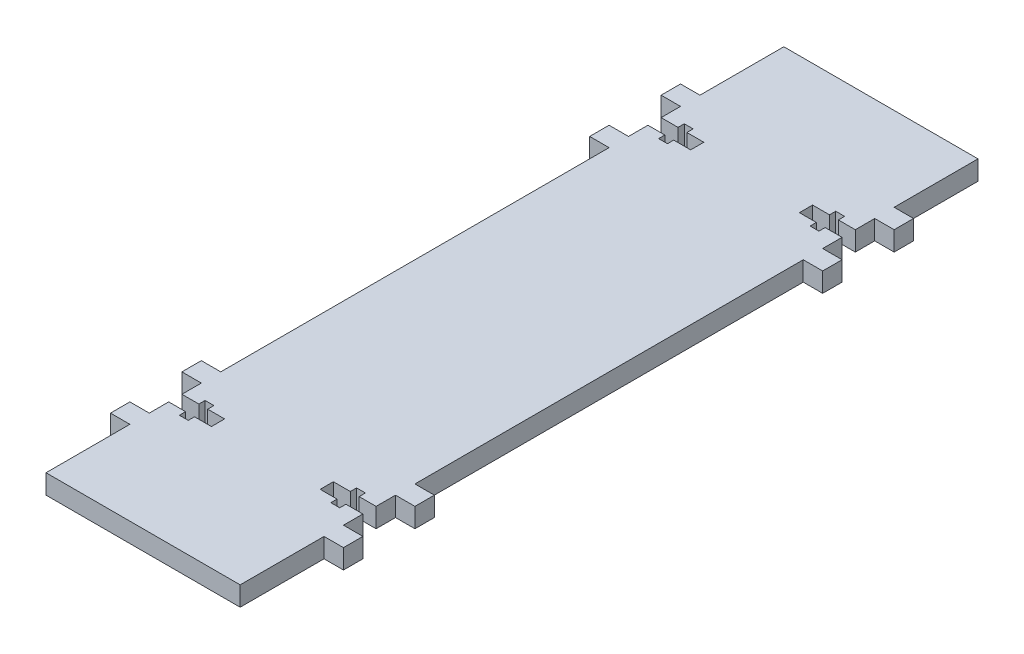
SolidWorks part; units mm, degrees
ref_plane "Front Plane" through (0, 0, 0) normal (0, 0, 1) x (1, 0, 0)
ref_plane "Top Plane" through (0, 0, 0) normal (0, 1, 0) x (1, 0, 0)
ref_plane "Right Plane" through (0, 0, 0) normal (1, 0, 0) x (0, 0, -1)
sketch "Elevator Belt Backplate" plane through (0, 0, 0) normal (0, 1, 0) x (1, 0, 0)
  line L0 (-31.75, -63.5) -> (-31.75, 63.5)
  line L1 (-31.75, -120.65) -> (31.75, -120.65)
  line L2 (-31.75, -93.218) -> (-31.75, -120.65)
  line L3 (-31.75, 120.65) -> (31.75, 120.65)
  line L4 (31.75, -120.65) -> (31.75, -93.218)
  line L5 (-31.75, -120.65) -> (31.75, 120.65) construction
  line L6 (-31.75, 120.65) -> (31.75, -120.65) construction
  line L7 (31.75, 93.218) -> (31.75, 120.65)
  line L9 (0, 120.65) -> (0, -120.65) construction
  line L21 (-31.75, 93.218) -> (-31.75, 120.65)
  line L70 (31.75, -63.5) -> (31.75, 63.5)
  point P0 (0, 0)
  line B0 (31.75, 69.85) -> (38.1, 69.85)
  line B1 (38.1, 69.85) -> (38.1, 63.5)
  line B2 (38.1, 63.5) -> (31.75, 63.5)
  line B3 (31.75, 76.2) -> (26.215, 76.2)
  line B4 (26.215, 76.2) -> (26.215, 74.159)
  line B5 (26.215, 74.159) -> (23.315, 74.159)
  line B6 (23.315, 74.159) -> (23.315, 76.2)
  line B7 (23.315, 76.2) -> (17.78, 76.2)
  line B8 (17.78, 76.2) -> (17.78, 80.518)
  line B9 (17.78, 80.518) -> (23.315, 80.518)
  line B10 (23.315, 80.518) -> (23.315, 82.559)
  line B11 (23.315, 82.559) -> (26.215, 82.559)
  line B12 (26.215, 82.559) -> (26.215, 80.518)
  line B13 (26.215, 80.518) -> (31.75, 80.518)
  line B14 (17.78, 78.359) -> (31.75, 78.359) construction
  line B15 (31.75, 86.868) -> (31.75, 80.518)
  line B16 (38.1, 93.218) -> (31.75, 93.218)
  line B17 (31.75, 69.85) -> (31.75, 76.2)
  line B18 (38.1, 86.868) -> (38.1, 93.218)
  line B19 (31.75, 86.868) -> (38.1, 86.868)
  line B20 (31.75, -69.85) -> (38.1, -69.85)
  line B21 (38.1, -69.85) -> (38.1, -63.5)
  line B22 (38.1, -63.5) -> (31.75, -63.5)
  line B23 (31.75, -76.2) -> (26.215, -76.2)
  line B24 (26.215, -76.2) -> (26.215, -74.159)
  line B25 (26.215, -74.159) -> (23.315, -74.159)
  line B26 (23.315, -74.159) -> (23.315, -76.2)
  line B27 (23.315, -76.2) -> (17.78, -76.2)
  line B28 (17.78, -76.2) -> (17.78, -80.518)
  line B29 (17.78, -80.518) -> (23.315, -80.518)
  line B30 (23.315, -80.518) -> (23.315, -82.559)
  line B31 (23.315, -82.559) -> (26.215, -82.559)
  line B32 (26.215, -82.559) -> (26.215, -80.518)
  line B33 (26.215, -80.518) -> (31.75, -80.518)
  line B34 (17.78, -78.359) -> (31.75, -78.359) construction
  line B35 (31.75, -86.868) -> (31.75, -80.518)
  line B36 (38.1, -93.218) -> (31.75, -93.218)
  line B37 (31.75, -69.85) -> (31.75, -76.2)
  line B38 (38.1, -86.868) -> (38.1, -93.218)
  line B39 (31.75, -86.868) -> (38.1, -86.868)
  line B40 (-31.75, -69.85) -> (-38.1, -69.85)
  line B41 (-38.1, -69.85) -> (-38.1, -63.5)
  line B42 (-38.1, -63.5) -> (-31.75, -63.5)
  line B43 (-31.75, -76.2) -> (-26.215, -76.2)
  line B44 (-26.215, -76.2) -> (-26.215, -74.159)
  line B45 (-26.215, -74.159) -> (-23.315, -74.159)
  line B46 (-23.315, -74.159) -> (-23.315, -76.2)
  line B47 (-23.315, -76.2) -> (-17.78, -76.2)
  line B48 (-17.78, -76.2) -> (-17.78, -80.518)
  line B49 (-17.78, -80.518) -> (-23.315, -80.518)
  line B50 (-23.315, -80.518) -> (-23.315, -82.559)
  line B51 (-23.315, -82.559) -> (-26.215, -82.559)
  line B52 (-26.215, -82.559) -> (-26.215, -80.518)
  line B53 (-26.215, -80.518) -> (-31.75, -80.518)
  line B54 (-17.78, -78.359) -> (-31.75, -78.359) construction
  line B55 (-31.75, -86.868) -> (-31.75, -80.518)
  line B56 (-38.1, -93.218) -> (-31.75, -93.218)
  line B57 (-31.75, -69.85) -> (-31.75, -76.2)
  line B58 (-38.1, -86.868) -> (-38.1, -93.218)
  line B59 (-31.75, -86.868) -> (-38.1, -86.868)
  line B60 (-31.75, 69.85) -> (-38.1, 69.85)
  line B61 (-38.1, 69.85) -> (-38.1, 63.5)
  line B62 (-38.1, 63.5) -> (-31.75, 63.5)
  line B63 (-31.75, 76.2) -> (-26.215, 76.2)
  line B64 (-26.215, 76.2) -> (-26.215, 74.159)
  line B65 (-26.215, 74.159) -> (-23.315, 74.159)
  line B66 (-23.315, 74.159) -> (-23.315, 76.2)
  line B67 (-23.315, 76.2) -> (-17.78, 76.2)
  line B68 (-17.78, 76.2) -> (-17.78, 80.518)
  line B69 (-17.78, 80.518) -> (-23.315, 80.518)
  line B70 (-23.315, 80.518) -> (-23.315, 82.559)
  line B71 (-23.315, 82.559) -> (-26.215, 82.559)
  line B72 (-26.215, 82.559) -> (-26.215, 80.518)
  line B73 (-26.215, 80.518) -> (-31.75, 80.518)
  line B74 (-17.78, 78.359) -> (-31.75, 78.359) construction
  line B75 (-31.75, 86.868) -> (-31.75, 80.518)
  line B76 (-38.1, 93.218) -> (-31.75, 93.218)
  line B77 (-31.75, 69.85) -> (-31.75, 76.2)
  line B78 (-38.1, 86.868) -> (-38.1, 93.218)
  line B79 (-31.75, 86.868) -> (-38.1, 86.868)
  dimension "D1" = 63.5
  dimension "D2" = 63.5
  dimension "D4" = 63.5
  dimension "D5" = 241.3
sketch_block_instance "Male T-slot assembly-1"
sketch_block "Male T-slot assembly" parameters "D1"=6.35, "D2"=6.35, "D3"=4.318, "D4"=2.9, "D5"=8.4, "D6"=13.97, "D7"=6.35
sketch_block_instance "Male T-slot assembly-3"
sketch_block_instance "Male T-slot assembly-10"
sketch_block_instance "Male T-slot assembly-11"
extrude "Boss-Extrude1" add sketch "Elevator Belt Backplate" along normal blind 6.35 contours B79 B75 B73 B72 B71 B70 B69 B68 B67 B66 B65 B64 B63 B77 B60 B61 B62 L0 B42 B41 B40 B57 B43 B44 B45 B46 B47 B48 B49 B50 B51 B52 B53 B55 B59 B58 B56 L2 L1 L4 B36 B38 B39 B35 B33 B32 B31 B30 B29 B28 B27 region at (0, 0, 0)
equation "\"Ball Diameter\"= 1.75in"
equation "\"Sheet Thickness\"= 0.25in"
equation "\"Screw Diameter\"= .17in"
equation "\"Robot Diameter\"= 14in"
equation "\"Castor Screw Diameter\"= 0.22in"
equation "\"Wheel Diameter\" = 4in"
equation "\"Nut Diameter\" = 8.4mm"
equation "\"Nut Height\" = 2.9mm"
equation "\"Screw Height\" = 0.55in"
equation "\"Pulley Diameter\" = 1in"
equation "\"Reactor Height\" = 14in"
equation "\"Elevator Height\" = 11.5in"
equation "\"Elevator Width\" = \"Ball Diameter\" + 0.25in"
equation "\"Elevator Bearing Diameter\" = sqr(2*(\"Sheet Thickness\"^2)) + 0.2in"
equation "\"Elevator Axle Length\" = \"Elevator Width\" + 8*\"Sheet Thickness\""
equation "\"D7@Elevator Belt Backplate\"=\"Sheet Thickness\""
equation "\"D8@Elevator Belt Backplate\"=\"Sheet Thickness\""
equation "\"D4@Elevator Belt Backplate\"=\"Elevator Width\" + 2 * \"Sheet Thickness\""
equation "\"D5@Elevator Belt Backplate\"=\"Elevator Height\"-\"Pulley Diameter\"-1in"
equation "\"D1@Boss-Extrude1\"=\"Sheet Thickness\""
